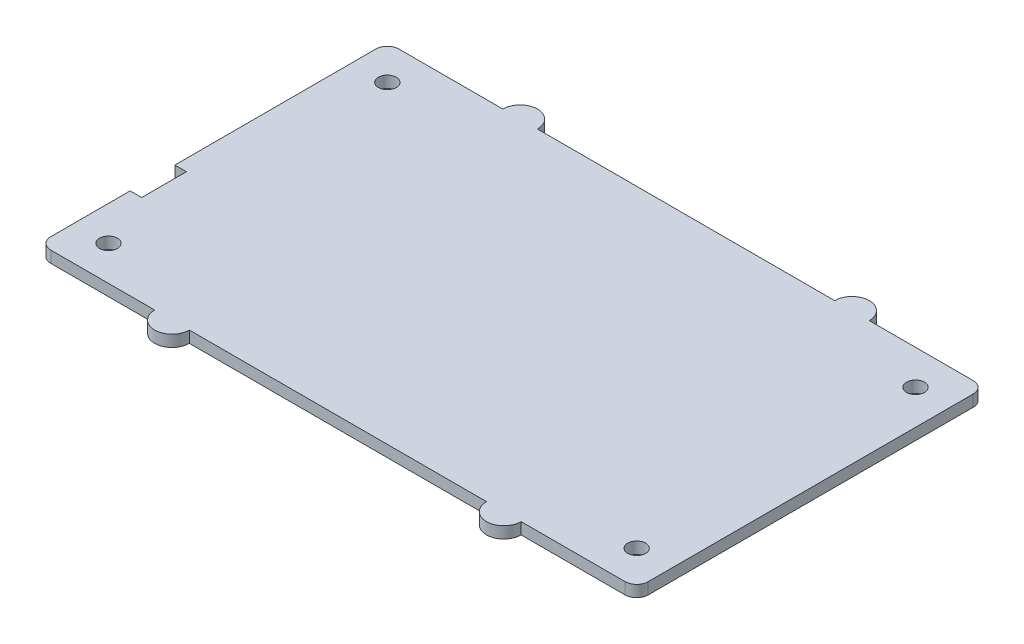
SolidWorks part; units mm, degrees
ref_plane "前视基准面" through (0, 0, 0) normal (0, 0, 1) x (1, 0, 0)
ref_plane "上视基准面" through (0, 0, 0) normal (0, 1, 0) x (1, 0, 0)
ref_plane "右视基准面" through (0, 0, 0) normal (1, 0, 0) x (0, 0, -1)
sketch "草图1" plane through (0, 0, 0) normal (0, 1, 0) x (1, 0, 0)
  line L0 (0, 0) -> (-12.7865, 0) construction
  line L1 (0, 0) -> (0, 22.3168) construction
  line L2 (91.46, 0) -> (91.46, 15.7584) construction
  line L3 (91.46, 48.29) -> (79.4981, 48.29) construction
  line L4 (-6, 0) -> (-6, 22.3168) construction
  line L5 (0, -6) -> (-12.7865, -6) construction
  line L6 (91.46, 54.29) -> (79.4981, 54.29) construction
  line L7 (97.46, 0) -> (97.46, 15.7584) construction
  line L8 (95.46, 54.29) -> (-4, 54.29)
  line L9 (-6, 52.29) -> (-6, -4)
  line L10 (-4, -6) -> (95.46, -6)
  line L11 (97.46, -4) -> (97.46, 52.29)
  line L12 (0, -9) -> (-12.7865, -9) construction
  line L13 (14, 0) -> (14, 22.3168) construction
  line L14 (34, 0) -> (34, 22.3168) construction
  line L15 (77.46, 0) -> (77.46, 15.7584) construction
  line L16 (57.46, 0) -> (57.46, 15.7584) construction
  line L17 (91.46, 57.29) -> (79.4981, 57.29) construction
  line L18 (0, 9.75) -> (-12.7865, 9.75) construction
  line L19 (0, 17.45) -> (-12.7865, 17.45) construction
  line L20 (-4, 52.29) -> (-4, -4) construction
  line L22 (-6, 17.4939) -> (-4, 17.4939)
  line L23 (-6, 17.4939) -> (-6, 9.75)
  line L24 (-6, 9.75) -> (-4, 9.75)
  line L25 (-4, 17.4939) -> (-4, 9.75)
  circle A0 centre (0, 0) radius 1.55
  circle A1 centre (91.46, 0) radius 1.55
  circle A2 centre (91.46, 48.29) radius 1.55
  circle A3 centre (0, 48.29) radius 1.55
  circle A4 centre (-4, 52.29) radius 2
  circle A5 centre (-4, -4) radius 2
  circle A6 centre (95.46, -4) radius 2
  circle A7 centre (95.46, 52.29) radius 2
  circle A8 centre (17, 54.29) radius 3
  circle A11 centre (74.46, 54.29) radius 3
  circle A12 centre (17, -6) radius 3
  circle A15 centre (74.46, -6) radius 3
  dimension "D1" = 2
  dimension "D9" = 20
  dimension "D7" = 3
  dimension "D13" = 15.75
  dimension "D8" = 20
  dimension "D3" = 6
  dimension "D4" = 6
  dimension "D5" = 6
  dimension "D6" = 6
  dimension "D10" = 20
  dimension "D11" = 20
  dimension "D12" = 3
  dimension "D14" = 7.7
  dimension "D15" = 2
  dimension "D2" = 2
extrude "凸台-拉伸1" add sketch "草图1" along normal blind 2 contours A7 L8 A4 L9 A5 L10 A6 L11 A3 A2 A1 A0 | A5 | A4 | A7 | A6 | A8 | A11 | A15 | A12 region at (45.8592, 0, -24.1718) region at (95.46, 0, -52.29) region at (95.46, 0, 4) region at (-4, 0, -52.29) region at (-4, 0, 4)
